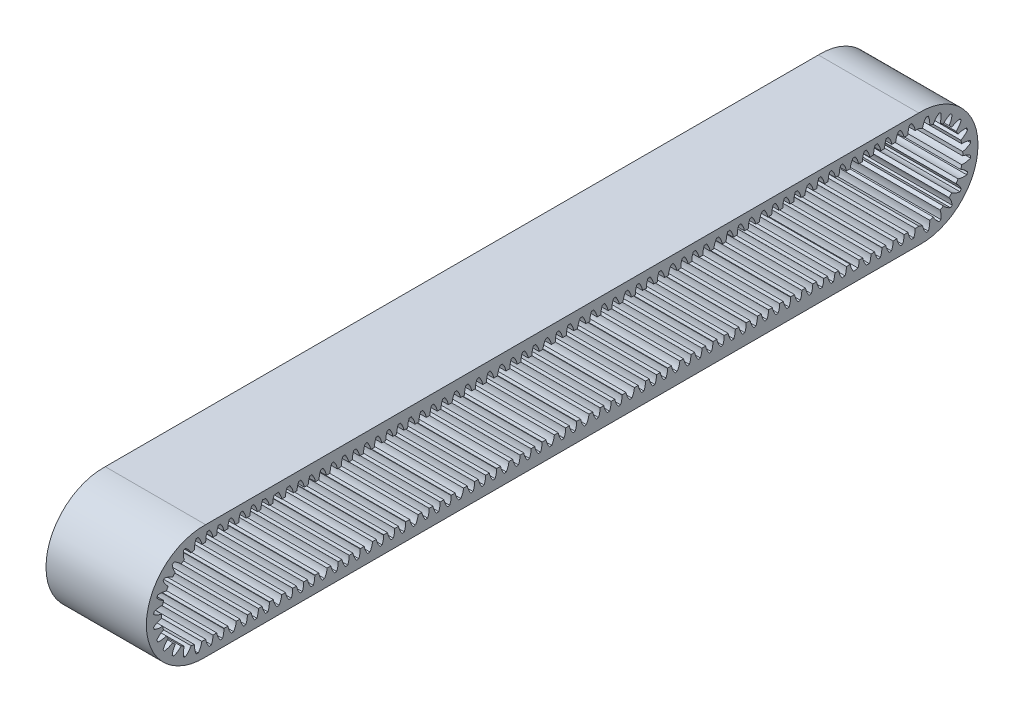
SolidWorks part; units mm, degrees
material "Rubber"
ref_plane "Front Plane" through (0, 0, 0) normal (0, 0, 1) x (1, 0, 0)
ref_plane "Top Plane" through (0, 0, 0) normal (0, 1, 0) x (1, 0, 0)
ref_plane "Right Plane" through (0, 0, 0) normal (1, 0, 0) x (0, 0, -1)
ref_plane "Plane1" through (-24.0362, 0, 0) normal (1, 0, 0) x (0, 0, -1)
sketch "Sketch1" plane through (-24.0362, 0, 0) normal (1, 0, 0) x (0, 0, -1)
  line L0 (112.0321, 33.7741) -> (-86.9109, 33.7741)
  line L5 (-86.9109, 1.7916) -> (112.0321, 1.7916)
  line L7 (-87.9491, 6.0912) -> (-87.9679, 6.0447)
  line L10 (-81.7512, 6.1541) -> (-81.8028, 6.0893)
  line L11 (-86.9109, 29.521) -> (-86.8764, 29.6927)
  line L15 (-72.2002, 6.1642) -> (-72.2019, 6.1661)
  line L16 (-69.0763, 6.229) -> (-69.1279, 6.1642)
  line L18 (-65.6746, 6.229) -> (-65.6799, 6.2313)
  line L20 (-75.2742, 6.1661) -> (-75.2826, 6.1564)
  line L22 (-59.5315, 6.2693) -> (-59.5332, 6.2712)
  line L23 (-56.4075, 6.3341) -> (-56.4592, 6.2693)
  line L25 (-53.0059, 6.3341) -> (-53.0112, 6.3364)
  line L27 (-46.8565, 6.3442) -> (-46.8582, 6.3461)
  line L28 (-43.7326, 6.409) -> (-43.7842, 6.3442)
  line L30 (-40.3309, 6.409) -> (-40.3363, 6.4113)
  line L32 (-49.9305, 6.3461) -> (-49.9389, 6.3364)
  line L33 (-62.6055, 6.2712) -> (-62.6077, 6.2313)
  line L35 (-34.1561, 6.4872) -> (-34.1579, 6.4891)
  line L36 (-31.0322, 6.5521) -> (-31.0839, 6.4872)
  line L38 (-27.6306, 6.5521) -> (-27.6359, 6.5543)
  line L40 (-21.4812, 6.5622) -> (-21.4829, 6.5641)
  line L41 (-18.3573, 6.627) -> (-18.4089, 6.5622)
  line L43 (-14.9556, 6.627) -> (-14.961, 6.6293)
  line L45 (-24.5552, 6.5641) -> (-24.5636, 6.5543)
  line L47 (-8.8125, 6.6673) -> (-8.8142, 6.6692)
  line L48 (-5.6886, 6.7321) -> (-5.7402, 6.6673)
  line L50 (-2.2869, 6.7321) -> (-2.2923, 6.7344)
  line L52 (3.8625, 6.7422) -> (3.8607, 6.7441)
  line L53 (6.9864, 6.807) -> (6.9347, 6.7422)
  line L55 (10.388, 6.807) -> (10.3827, 6.8093)
  line L57 (0.7885, 6.7441) -> (0.78, 6.7344)
  line L58 (-11.8865, 6.6692) -> (-11.8887, 6.6293)
  line L59 (-37.2301, 6.4891) -> (-37.264, 6.4113)
  line L61 (13.5155, 6.9308) -> (13.5138, 6.9327)
  line L62 (16.6394, 6.9956) -> (16.5878, 6.9308)
  line L64 (20.0411, 6.9956) -> (20.0357, 6.9979)
  line L66 (26.1905, 7.0057) -> (26.1887, 7.0076)
  line L67 (29.3144, 7.0705) -> (29.2627, 7.0057)
  line L69 (32.716, 7.0705) -> (32.7107, 7.0728)
  line L71 (23.1165, 7.0076) -> (23.108, 6.9979)
  line L73 (38.8592, 7.1108) -> (38.8575, 7.1127)
  line L74 (41.9831, 7.1756) -> (41.9315, 7.1108)
  line L76 (45.3847, 7.1756) -> (45.3794, 7.1779)
  line L78 (51.5341, 7.1857) -> (51.5324, 7.1876)
  line L79 (54.658, 7.2505) -> (54.6064, 7.1857)
  line L80 (13.0997, 4.781) -> (13.0408, 4.6577)
  line L81 (56.7243, 5.021) -> (56.7591, 4.9037)
  line L83 (48.4601, 7.1876) -> (48.4517, 7.1779)
  line L84 (35.7852, 7.1127) -> (35.783, 7.0728)
  line L85 (85.5453, 7.0189) -> (85.5297, 7.0033)
  line L86 (91.8615, 6.7472) -> (91.8607, 6.7465)
  line L87 (113.0891, 6.0447) -> (112.0981, 6.3763)
  line L88 (97.4226, 4.3147) -> (98.2668, 4.2409)
  line L91 (108.9883, 29.915) -> (109.0399, 29.9798)
  line L93 (105.5866, 29.915) -> (105.592, 29.9127)
  line L95 (99.4373, 29.9049) -> (99.439, 29.903)
  line L96 (96.3133, 29.8401) -> (96.365, 29.9049)
  line L98 (92.9117, 29.8401) -> (92.917, 29.8378)
  line L100 (102.5113, 29.903) -> (102.5197, 29.9127)
  line L102 (86.7685, 29.7998) -> (86.7703, 29.7979)
  line L103 (83.6446, 29.735) -> (83.6963, 29.7998)
  line L105 (80.243, 29.735) -> (80.2483, 29.7327)
  line L107 (74.0936, 29.7248) -> (74.0953, 29.7229)
  line L108 (70.9697, 29.66) -> (71.0213, 29.7248)
  line L110 (67.568, 29.66) -> (67.5734, 29.6577)
  line L112 (77.1676, 29.7229) -> (77.176, 29.7327)
  line L113 (89.8425, 29.7979) -> (89.8447, 29.8378)
  line L115 (61.3932, 29.5818) -> (61.3949, 29.5799)
  line L116 (58.2693, 29.517) -> (58.3209, 29.5818)
  line L118 (54.8677, 29.517) -> (54.873, 29.5147)
  line L120 (48.7183, 29.5069) -> (48.72, 29.505)
  line L121 (45.5944, 29.4421) -> (45.646, 29.5069)
  line L123 (42.1927, 29.4421) -> (42.1981, 29.4398)
  line L125 (51.7923, 29.505) -> (51.8007, 29.5147)
  line L127 (36.0496, 29.4018) -> (36.0513, 29.3999)
  line L128 (32.9257, 29.337) -> (32.9773, 29.4018)
  line L130 (29.524, 29.337) -> (29.5294, 29.3347)
  line L132 (23.3746, 29.3269) -> (23.3763, 29.3249)
  line L133 (20.2507, 29.262) -> (20.3023, 29.3269)
  line L135 (16.8491, 29.262) -> (16.8544, 29.2597)
  line L137 (26.4486, 29.3249) -> (26.4571, 29.3347)
  line L138 (39.1236, 29.3999) -> (39.1258, 29.4398)
  line L139 (64.4672, 29.5799) -> (64.5011, 29.6577)
  line L141 (13.7216, 29.1383) -> (13.7233, 29.1364)
  line L142 (10.5977, 29.0735) -> (10.6493, 29.1383)
  line L144 (7.196, 29.0735) -> (7.2014, 29.0712)
  line L146 (1.0466, 29.0634) -> (1.0483, 29.0615)
  line L147 (-2.0773, 28.9986) -> (-2.0257, 29.0634)
  line L149 (-5.4789, 28.9986) -> (-5.4736, 28.9963)
  line L151 (4.1206, 29.0615) -> (4.1291, 29.0712)
  line L153 (-11.6221, 28.9583) -> (-11.6204, 28.9564)
  line L154 (-14.746, 28.8935) -> (-14.6944, 28.9583)
  line L156 (-18.1476, 28.8935) -> (-18.1423, 28.8912)
  line L158 (-24.297, 28.8833) -> (-24.2953, 28.8814)
  line L159 (-27.4209, 28.8185) -> (-27.3693, 28.8833)
  line L160 (14.1374, 31.288) -> (14.1963, 31.4114)
  line L161 (-29.4872, 31.0481) -> (-29.522, 31.1653)
  line L163 (-21.223, 28.8814) -> (-21.2146, 28.8912)
  line L164 (-8.5481, 28.9564) -> (-8.5459, 28.9963)
  line L165 (-58.3082, 29.0501) -> (-58.2926, 29.0658)
  line L166 (-64.6244, 29.3219) -> (-64.6236, 29.3226)
  line L167 (-70.1855, 31.7543) -> (-71.0297, 31.8281)
  line L168 (112.1122, 29.9798) -> (113.0891, 29.521)
  line L170 (57.7751, 7.1388) -> (57.7651, 7.1333)
  line L171 (63.9422, 7.1361) -> (63.8989, 7.1096)
  line L172 (67.0233, 7.1807) -> (67.0145, 7.1361)
  line L173 (70.1389, 7.1622) -> (70.0956, 7.1807)
  line L174 (76.3286, 7.2109) -> (76.2799, 7.1225)
  line L175 (79.3925, 7.2482) -> (79.4009, 7.2109)
  line L176 (82.4648, 7.2482) -> (82.4552, 7.2604)
  line L178 (101.7757, 6.3899) -> (101.7324, 6.3634)
  line L179 (104.8569, 6.4345) -> (104.848, 6.3899)
  line L180 (107.9724, 6.416) -> (107.9292, 6.4345)
  line L181 (-30.5281, 28.9358) -> (-30.538, 28.9303)
  line L182 (-36.6618, 28.9594) -> (-36.7051, 28.9329)
  line L183 (-39.7774, 28.9329) -> (-39.7862, 28.8884)
  line L184 (-42.8585, 28.8884) -> (-42.9018, 28.9069)
  line L185 (-49.0429, 28.9466) -> (-49.0915, 28.8581)
  line L186 (-52.1638, 28.8581) -> (-52.1555, 28.8209)
  line L187 (-55.2181, 28.8087) -> (-55.2277, 28.8209)
  line L188 (-74.4953, 29.7056) -> (-74.5386, 29.6791)
  line L189 (-77.6109, 29.6791) -> (-77.6198, 29.6346)
  line L191 (-80.6921, 29.6346) -> (-80.7353, 29.6531)
  line L193 (-84.8768, 6.0893) -> (-84.8751, 6.0893)
  line L194 (-78.3438, 6.1559) -> (-78.3495, 6.1541)
  arc A0 (-101.4071, 19.3207) -> (-99.1775, 18.3113) centre (-98.3303, 23.1498) ccw
  arc A2 (-84.8751, 6.0893) -> (-83.8182, 6.0893) centre (-84.3466, 17.8274) ccw
  arc A6 (-87.9491, 6.0912) -> (-86.8922, 6.0912) centre (-87.4206, 17.8293) ccw
  arc A7 (-86.8922, 6.0912) -> (-85.8828, 3.8616) centre (-82.0537, 6.9383) ccw
  arc A8 (-85.8828, 3.8616) -> (-85.2909, 3.9395) centre (-87.4206, 17.8293) ccw
  arc A9 (-85.2909, 3.9395) -> (-84.8768, 6.0893) centre (-89.7859, 5.9204) ccw
  arc A10 (-83.8182, 6.0893) -> (-82.8088, 3.8597) centre (-78.9797, 6.9364) ccw
  arc A11 (-82.8088, 3.8597) -> (-82.217, 3.9376) centre (-84.3466, 17.8274) ccw
  arc A12 (-82.217, 3.9376) -> (-81.8028, 6.0893) centre (-86.7119, 5.9184) ccw
  arc A13 (-81.7512, 6.1541) -> (-80.6943, 6.1541) centre (-81.2227, 17.8922) ccw
  arc A14 (-80.6943, 6.1541) -> (-79.6849, 3.9245) centre (-75.8558, 7.0012) ccw
  arc A15 (-79.6849, 3.9245) -> (-79.093, 4.0024) centre (-81.2227, 17.8922) ccw
  arc A16 (-79.093, 4.0024) -> (-78.3495, 6.1541) centre (-83.2376, 6.6389) ccw
  arc A17 (-78.3438, 6.1559) -> (-77.298, 6.1564) centre (-77.8264, 17.8945) ccw
  arc A18 (-77.298, 6.1564) -> (-76.2886, 3.9268) centre (-72.4595, 7.0035) ccw
  arc A19 (-76.2886, 3.9268) -> (-75.6967, 4.0047) centre (-77.8264, 17.8945) ccw
  arc A20 (-75.6967, 4.0047) -> (-75.2826, 6.1564) centre (-80.1917, 5.9856) ccw
  arc A21 (-72.2002, 6.1642) -> (-71.1432, 6.1642) centre (-71.6717, 17.9023) ccw
  arc A22 (-75.2742, 6.1661) -> (-74.2172, 6.1661) centre (-74.7457, 17.9042) ccw
  arc A23 (-74.2172, 6.1661) -> (-73.2079, 3.9365) centre (-69.3787, 7.0133) ccw
  arc A24 (-73.2079, 3.9365) -> (-72.616, 4.0145) centre (-74.7457, 17.9042) ccw
  arc A25 (-72.616, 4.0145) -> (-72.2019, 6.1661) centre (-77.111, 5.9953) ccw
  arc A27 (113.0891, 6.0447) -> (114.0984, 3.8152) centre (117.9276, 6.8919) ccw
  arc A28 (114.0984, 3.8152) -> (114.6903, 3.8931) centre (112.5606, 17.7829) ccw
  arc A29 (114.6903, 3.8931) -> (115.0882, 6.3079) centre (110.1953, 5.8739) ccw
  arc A30 (115.0882, 6.3079) -> (116.1091, 6.5815) centre (112.5606, 17.7829) ccw
  arc A31 (116.1091, 6.5815) -> (117.6611, 4.6891) centre (120.5635, 8.6521) ccw
  arc A32 (117.6611, 4.6891) -> (118.2127, 4.9176) centre (112.5606, 17.7829) ccw
  arc A33 (118.2127, 4.9176) -> (117.972, 7.3531) centre (113.3582, 5.6675) ccw
  arc A34 (117.972, 7.3531) -> (118.8873, 7.8816) centre (112.5606, 17.7829) ccw
  arc A35 (118.8873, 7.8816) -> (120.8762, 6.4554) centre (122.654, 11.0345) ccw
  arc A36 (120.8762, 6.4554) -> (121.3499, 6.8188) centre (112.5606, 17.7829) ccw
  arc A37 (121.3499, 6.8188) -> (120.487, 9.1091) centre (116.4667, 6.2868) ccw
  arc A38 (120.487, 9.1091) -> (121.2344, 9.8564) centre (112.5606, 17.7829) ccw
  arc A39 (121.2344, 9.8564) -> (123.5246, 8.9936) centre (124.0567, 13.8768) ccw
  arc A40 (123.5246, 8.9936) -> (123.8881, 9.4672) centre (112.5606, 17.7829) ccw
  arc A41 (123.8881, 9.4672) -> (122.4619, 11.4561) centre (119.309, 7.6895) ccw
  arc A42 (122.4619, 11.4561) -> (122.9903, 12.3715) centre (112.5606, 17.7829) ccw
  arc A43 (122.9903, 12.3715) -> (125.4259, 12.1308) centre (124.6759, 16.9853) ccw
  arc A44 (125.4259, 12.1308) -> (125.6543, 12.6823) centre (112.5606, 17.7829) ccw
  arc A45 (125.6543, 12.6823) -> (123.762, 14.2343) centre (121.6914, 9.78) ccw
  arc A46 (123.762, 14.2343) -> (124.0355, 15.2553) centre (112.5606, 17.7829) ccw
  arc A47 (124.0355, 15.2553) -> (126.4504, 15.6532) centre (124.4695, 20.1481) ccw
  arc A48 (126.4504, 15.6532) -> (126.5283, 16.245) centre (112.5606, 17.7829) ccw
  arc A49 (126.5283, 16.245) -> (124.2987, 17.2544) centre (123.4516, 12.4159) ccw
  arc A50 (124.2987, 17.2544) -> (124.2987, 18.3113) centre (112.5606, 17.7829) ccw
  arc A51 (124.2987, 18.3113) -> (126.5283, 19.3207) centre (123.4516, 23.1498) ccw
  arc A52 (126.5283, 19.3207) -> (126.4504, 19.9125) centre (112.5606, 17.7829) ccw
  arc A53 (126.4504, 19.9125) -> (124.0355, 20.3104) centre (124.4695, 15.4176) ccw
  arc A54 (124.0355, 20.3104) -> (123.762, 21.3314) centre (112.5606, 17.7829) ccw
  arc A55 (123.762, 21.3314) -> (125.6543, 22.8834) centre (121.6914, 25.7857) ccw
  arc A56 (125.6543, 22.8834) -> (125.4259, 23.4349) centre (112.5606, 17.7829) ccw
  arc A57 (125.4259, 23.4349) -> (122.9903, 23.1942) centre (124.6759, 18.5804) ccw
  arc A58 (122.9903, 23.1942) -> (122.4619, 24.1096) centre (112.5606, 17.7829) ccw
  arc A59 (122.4619, 24.1096) -> (123.8881, 26.0985) centre (119.309, 27.8762) ccw
  arc A60 (123.8881, 26.0985) -> (123.5246, 26.5721) centre (112.5606, 17.7829) ccw
  arc A61 (123.5246, 26.5721) -> (121.2344, 25.7093) centre (124.0567, 21.6889) ccw
  arc A62 (121.2344, 25.7093) -> (120.487, 26.4566) centre (112.5606, 17.7829) ccw
  arc A63 (120.487, 26.4566) -> (121.3499, 28.7469) centre (116.4667, 29.2789) ccw
  arc A64 (121.3499, 28.7469) -> (120.8762, 29.1103) centre (112.5606, 17.7829) ccw
  arc A65 (120.8762, 29.1103) -> (118.8873, 27.6841) centre (122.654, 24.5312) ccw
  arc A66 (118.8873, 27.6841) -> (117.972, 28.2126) centre (112.5606, 17.7829) ccw
  arc A67 (117.972, 28.2126) -> (118.2127, 30.6481) centre (113.3582, 29.8982) ccw
  arc A68 (118.2127, 30.6481) -> (117.6611, 30.8766) centre (112.5606, 17.7829) ccw
  arc A69 (117.6611, 30.8766) -> (116.1091, 28.9842) centre (120.5635, 26.9136) ccw
  arc A70 (116.1091, 28.9842) -> (115.0882, 29.2578) centre (112.5606, 17.7829) ccw
  arc A71 (115.0882, 29.2578) -> (114.6903, 31.6726) centre (110.1953, 29.6918) ccw
  arc A72 (114.6903, 31.6726) -> (114.0984, 31.7505) centre (112.5606, 17.7829) ccw
  arc A73 (114.0984, 31.7505) -> (113.0891, 29.521) centre (117.9276, 28.6738) ccw
  arc A75 (-71.1432, 6.1642) -> (-70.1339, 3.9346) centre (-66.3047, 7.0114) ccw
  arc A76 (-70.1339, 3.9346) -> (-69.542, 4.0125) centre (-71.6717, 17.9023) ccw
  arc A77 (-69.542, 4.0125) -> (-69.1279, 6.1642) centre (-74.037, 5.9934) ccw
  arc A78 (-69.0763, 6.229) -> (-68.0193, 6.229) centre (-68.5478, 17.9671) ccw
  arc A79 (-68.0193, 6.229) -> (-67.01, 3.9994) centre (-63.1808, 7.0762) ccw
  arc A80 (-67.01, 3.9994) -> (-66.4181, 4.0774) centre (-68.5478, 17.9671) ccw
  arc A81 (-66.4181, 4.0774) -> (-65.6746, 6.229) centre (-70.5627, 6.7138) ccw
  arc A82 (-65.6799, 6.2313) -> (-64.623, 6.2313) centre (-65.1515, 17.9694) ccw
  arc A83 (-64.623, 6.2313) -> (-63.6137, 4.0017) centre (-59.7845, 7.0785) ccw
  arc A84 (-63.6137, 4.0017) -> (-63.0218, 4.0797) centre (-65.1515, 17.9694) ccw
  arc A85 (-63.0218, 4.0797) -> (-62.6077, 6.2313) centre (-67.5168, 6.0605) ccw
  arc A86 (-59.5315, 6.2693) -> (-58.4745, 6.2693) centre (-59.003, 18.0074) ccw
  arc A87 (-62.6055, 6.2712) -> (-61.5485, 6.2712) centre (-62.077, 18.0093) ccw
  arc A88 (-61.5485, 6.2712) -> (-60.5392, 4.0416) centre (-56.71, 7.1184) ccw
  arc A89 (-60.5392, 4.0416) -> (-59.9473, 4.1196) centre (-62.077, 18.0093) ccw
  arc A90 (-59.9473, 4.1196) -> (-59.5332, 6.2712) centre (-64.4423, 6.1004) ccw
  arc A91 (-58.4745, 6.2693) -> (-57.4652, 4.0397) centre (-53.636, 7.1165) ccw
  arc A92 (-57.4652, 4.0397) -> (-56.8733, 4.1176) centre (-59.003, 18.0074) ccw
  arc A93 (-56.8733, 4.1176) -> (-56.4592, 6.2693) centre (-61.3683, 6.0985) ccw
  arc A94 (-56.4075, 6.3341) -> (-55.3506, 6.3341) centre (-55.8791, 18.0722) ccw
  arc A95 (-55.3506, 6.3341) -> (-54.3413, 4.1045) centre (-50.5121, 7.1813) ccw
  arc A96 (-54.3413, 4.1045) -> (-53.7494, 4.1825) centre (-55.8791, 18.0722) ccw
  arc A97 (112.0321, 1.7916) -> (112.0321, 33.7741) centre (112.5606, 17.7829) ccw
  arc A98 (-99.1775, 18.3113) -> (-99.1775, 17.2544) centre (-87.4394, 17.7829) ccw
  arc A99 (-99.1775, 17.2544) -> (-101.4071, 16.245) centre (-98.3303, 12.4159) ccw
  arc A100 (-101.4071, 16.245) -> (-101.3291, 15.6532) centre (-87.4394, 17.7829) ccw
  arc A101 (-101.3291, 15.6532) -> (-98.9143, 15.2553) centre (-99.3483, 20.1481) ccw
  arc A102 (-98.9143, 15.2553) -> (-98.6408, 14.2343) centre (-87.4394, 17.7829) ccw
  arc A103 (-98.6408, 14.2343) -> (-100.5331, 12.6823) centre (-96.5702, 9.78) ccw
  arc A104 (-100.5331, 12.6823) -> (-100.2851, 12.0865) centre (-87.4394, 17.7829) ccw
  arc A105 (-100.2851, 12.0865) -> (-97.8691, 12.3715) centre (-99.6347, 16.9553) ccw
  arc A106 (-97.8691, 12.3715) -> (-97.3407, 11.4561) centre (-87.4394, 17.7829) ccw
  arc A107 (-97.3407, 11.4561) -> (-98.7668, 9.4672) centre (-94.1878, 7.6895) ccw
  arc A108 (-98.7668, 9.4672) -> (-98.4034, 8.9936) centre (-87.4394, 17.7829) ccw
  arc A109 (-98.4034, 8.9936) -> (-96.1132, 9.8564) centre (-98.9355, 13.8768) ccw
  arc A110 (-96.1132, 9.8564) -> (-95.3658, 9.1091) centre (-87.4394, 17.7829) ccw
  arc A111 (-95.3658, 9.1091) -> (-96.2286, 6.8188) centre (-91.3454, 6.2868) ccw
  arc A112 (-96.2286, 6.8188) -> (-95.755, 6.4554) centre (-87.4394, 17.7829) ccw
  arc A113 (-95.755, 6.4554) -> (-93.7661, 7.8816) centre (-97.5328, 11.0345) ccw
  arc A114 (-93.7661, 7.8816) -> (-92.8508, 7.3531) centre (-87.4394, 17.7829) ccw
  arc A115 (-92.8508, 7.3531) -> (-93.0914, 4.9176) centre (-88.2369, 5.6675) ccw
  arc A116 (-93.0914, 4.9176) -> (-92.5399, 4.6891) centre (-87.4394, 17.7829) ccw
  arc A117 (-92.5399, 4.6891) -> (-90.9879, 6.5815) centre (-95.4422, 8.6521) ccw
  arc A118 (-90.9879, 6.5815) -> (-89.967, 6.3079) centre (-87.4394, 17.7829) ccw
  arc A119 (-89.967, 6.3079) -> (-89.5691, 3.8931) centre (-85.0741, 5.8739) ccw
  arc A120 (-89.5691, 3.8931) -> (-88.9772, 3.8152) centre (-87.4394, 17.7829) ccw
  arc A121 (-88.9772, 3.8152) -> (-87.9679, 6.0447) centre (-92.8063, 6.8919) ccw
  arc A170 (-86.9109, 29.521) -> (-87.9679, 29.521) centre (-87.4394, 17.7829) ccw
  arc A171 (-87.9679, 29.521) -> (-88.9772, 31.7505) centre (-92.8063, 28.6738) ccw
  arc A172 (-88.9772, 31.7505) -> (-89.5691, 31.6726) centre (-87.4394, 17.7829) ccw
  arc A173 (-89.5691, 31.6726) -> (-89.967, 29.2578) centre (-85.0741, 29.6918) ccw
  arc A174 (-89.967, 29.2578) -> (-90.9879, 28.9842) centre (-87.4394, 17.7829) ccw
  arc A175 (-90.9879, 28.9842) -> (-92.5399, 30.8766) centre (-95.4422, 26.9136) ccw
  arc A176 (-92.5399, 30.8766) -> (-93.0914, 30.6481) centre (-87.4394, 17.7829) ccw
  arc A177 (-93.0914, 30.6481) -> (-92.8508, 28.2126) centre (-88.2369, 29.8982) ccw
  arc A178 (-92.8508, 28.2126) -> (-93.7661, 27.6841) centre (-87.4394, 17.7829) ccw
  arc A179 (-93.7661, 27.6841) -> (-95.755, 29.1103) centre (-97.5328, 24.5312) ccw
  arc A180 (-95.755, 29.1103) -> (-96.2286, 28.7469) centre (-87.4394, 17.7829) ccw
  arc A181 (-96.2286, 28.7469) -> (-95.3658, 26.4566) centre (-91.3454, 29.2789) ccw
  arc A182 (-95.3658, 26.4566) -> (-96.1132, 25.7093) centre (-87.4394, 17.7829) ccw
  arc A183 (-96.1132, 25.7093) -> (-98.4034, 26.5721) centre (-98.9355, 21.6889) ccw
  arc A184 (-98.4034, 26.5721) -> (-98.7668, 26.0985) centre (-87.4394, 17.7829) ccw
  arc A185 (-98.7668, 26.0985) -> (-97.3407, 24.1096) centre (-94.1878, 27.8762) ccw
  arc A186 (-97.3407, 24.1096) -> (-97.8691, 23.1942) centre (-87.4394, 17.7829) ccw
  arc A187 (-97.8691, 23.1942) -> (-100.3047, 23.4349) centre (-99.5547, 18.5804) ccw
  arc A188 (-100.3047, 23.4349) -> (-100.5331, 22.8834) centre (-87.4394, 17.7829) ccw
  arc A189 (-100.5331, 22.8834) -> (-98.6408, 21.3314) centre (-96.5702, 25.7857) ccw
  arc A190 (-98.6408, 21.3314) -> (-98.9143, 20.3104) centre (-87.4394, 17.7829) ccw
  arc A191 (-98.9143, 20.3104) -> (-101.3291, 19.9125) centre (-99.3483, 15.4176) ccw
  arc A192 (-101.3291, 19.9125) -> (-101.4071, 19.3207) centre (-87.4394, 17.7829) ccw
  arc A193 (-86.9109, 33.7741) -> (-86.9109, 1.7916) centre (-87.4394, 17.7829) ccw
  arc A388 (-53.7494, 4.1825) -> (-53.0059, 6.3341) centre (-57.894, 6.8189) ccw
  arc A389 (-53.0112, 6.3364) -> (-51.9543, 6.3364) centre (-52.4828, 18.0745) ccw
  arc A390 (-51.9543, 6.3364) -> (-50.945, 4.1068) centre (-47.1158, 7.1836) ccw
  arc A391 (-50.945, 4.1068) -> (-50.3531, 4.1848) centre (-52.4828, 18.0745) ccw
  arc A392 (-50.3531, 4.1848) -> (-49.9389, 6.3364) centre (-54.8481, 6.1656) ccw
  arc A393 (-46.8565, 6.3442) -> (-45.7996, 6.3442) centre (-46.328, 18.0823) ccw
  arc A394 (-49.9305, 6.3461) -> (-48.8736, 6.3461) centre (-49.402, 18.0842) ccw
  arc A395 (-48.8736, 6.3461) -> (-47.8642, 4.1166) centre (-44.0351, 7.1933) ccw
  arc A396 (-47.8642, 4.1166) -> (-47.2723, 4.1945) centre (-49.402, 18.0842) ccw
  arc A397 (-47.2723, 4.1945) -> (-46.8582, 6.3461) centre (-51.7673, 6.1753) ccw
  arc A398 (-45.7996, 6.3442) -> (-44.7902, 4.1147) centre (-40.9611, 7.1914) ccw
  arc A399 (-44.7902, 4.1147) -> (-44.1983, 4.1926) centre (-46.328, 18.0823) ccw
  arc A400 (-44.1983, 4.1926) -> (-43.7842, 6.3442) centre (-48.6933, 6.1734) ccw
  arc A401 (-43.7326, 6.409) -> (-42.6757, 6.409) centre (-43.2041, 18.1472) ccw
  arc A402 (-42.6757, 6.409) -> (-41.6663, 4.1795) centre (-37.8372, 7.2562) ccw
  arc A403 (-41.6663, 4.1795) -> (-41.0744, 4.2574) centre (-43.2041, 18.1472) ccw
  arc A404 (-41.0744, 4.2574) -> (-40.3309, 6.409) centre (-45.219, 6.8938) ccw
  arc A405 (-40.3363, 6.4113) -> (-39.2793, 6.4113) centre (-39.8078, 18.1494) ccw
  arc A406 (-39.2793, 6.4113) -> (-38.27, 4.1818) centre (-34.4409, 7.2585) ccw
  arc A407 (-38.27, 4.1818) -> (-37.6781, 4.2597) centre (-39.8078, 18.1494) ccw
  arc A408 (-37.6781, 4.2597) -> (-37.264, 6.4113) centre (-42.1731, 6.2405) ccw
  arc A409 (-34.1561, 6.4872) -> (-33.0992, 6.4872) centre (-33.6277, 18.2253) ccw
  arc A410 (-37.2301, 6.4891) -> (-36.1732, 6.4891) centre (-36.7017, 18.2273) ccw
  arc A411 (-36.1732, 6.4891) -> (-35.1639, 4.2596) centre (-31.3347, 7.3363) ccw
  arc A412 (-35.1639, 4.2596) -> (-34.572, 4.3375) centre (-36.7017, 18.2273) ccw
  arc A413 (-34.572, 4.3375) -> (-34.1579, 6.4891) centre (-39.067, 6.3183) ccw
  arc A414 (-33.0992, 6.4872) -> (-32.0899, 4.2577) centre (-28.2607, 7.3344) ccw
  arc A415 (-32.0899, 4.2577) -> (-31.498, 4.3356) centre (-33.6277, 18.2253) ccw
  arc A416 (-31.498, 4.3356) -> (-31.0839, 6.4872) centre (-35.993, 6.3164) ccw
  arc A417 (-31.0322, 6.5521) -> (-29.9753, 6.5521) centre (-30.5038, 18.2902) ccw
  arc A418 (-29.9753, 6.5521) -> (-28.966, 4.3225) centre (-25.1368, 7.3992) ccw
  arc A419 (-28.966, 4.3225) -> (-28.3741, 4.4004) centre (-30.5038, 18.2902) ccw
  arc A420 (-28.3741, 4.4004) -> (-27.6306, 6.5521) centre (-32.5187, 7.0368) ccw
  arc A421 (-27.6359, 6.5543) -> (-26.579, 6.5543) centre (-27.1075, 18.2924) ccw
  arc A422 (-26.579, 6.5543) -> (-25.5696, 4.3248) centre (-21.7405, 7.4015) ccw
  arc A423 (-25.5696, 4.3248) -> (-24.9778, 4.4027) centre (-27.1075, 18.2924) ccw
  arc A424 (-24.9778, 4.4027) -> (-24.5636, 6.5543) centre (-29.4728, 6.3835) ccw
  arc A425 (-21.4812, 6.5622) -> (-20.4243, 6.5622) centre (-20.9527, 18.3003) ccw
  arc A426 (-24.5552, 6.5641) -> (-23.4983, 6.5641) centre (-24.0267, 18.3022) ccw
  arc A427 (-23.4983, 6.5641) -> (-22.4889, 4.3345) centre (-18.6598, 7.4112) ccw
  arc A428 (-22.4889, 4.3345) -> (-21.897, 4.4124) centre (-24.0267, 18.3022) ccw
  arc A429 (-21.897, 4.4124) -> (-21.4829, 6.5641) centre (-26.392, 6.3933) ccw
  arc A430 (-20.4243, 6.5622) -> (-19.4149, 4.3326) centre (-15.5858, 7.4093) ccw
  arc A431 (-19.4149, 4.3326) -> (-18.823, 4.4105) centre (-20.9527, 18.3003) ccw
  arc A432 (-18.823, 4.4105) -> (-18.4089, 6.5622) centre (-23.318, 6.3914) ccw
  arc A433 (-18.3573, 6.627) -> (-17.3004, 6.627) centre (-17.8288, 18.3651) ccw
  arc A434 (-17.3004, 6.627) -> (-16.291, 4.3974) centre (-12.4619, 7.4741) ccw
  arc A435 (-16.291, 4.3974) -> (-15.6991, 4.4753) centre (-17.8288, 18.3651) ccw
  arc A436 (-15.6991, 4.4753) -> (-14.9556, 6.627) centre (-19.8437, 7.1118) ccw
  arc A437 (-14.961, 6.6293) -> (-13.904, 6.6293) centre (-14.4325, 18.3674) ccw
  arc A438 (-13.904, 6.6293) -> (-12.8947, 4.3997) centre (-9.0656, 7.4764) ccw
  arc A439 (-12.8947, 4.3997) -> (-12.3028, 4.4776) centre (-14.4325, 18.3674) ccw
  arc A440 (-12.3028, 4.4776) -> (-11.8887, 6.6293) centre (-16.7978, 6.4585) ccw
  arc A441 (-8.8125, 6.6673) -> (-7.7556, 6.6673) centre (-8.284, 18.4054) ccw
  arc A442 (-11.8865, 6.6692) -> (-10.8296, 6.6692) centre (-11.358, 18.4073) ccw
  arc A443 (-10.8296, 6.6692) -> (-9.8202, 4.4396) centre (-5.9911, 7.5163) ccw
  arc A444 (-9.8202, 4.4396) -> (-9.2283, 4.5175) centre (-11.358, 18.4073) ccw
  arc A445 (-9.2283, 4.5175) -> (-8.8142, 6.6692) centre (-13.7233, 6.4984) ccw
  arc A446 (-7.7556, 6.6673) -> (-6.7462, 4.4377) centre (-2.9171, 7.5144) ccw
  arc A447 (-6.7462, 4.4377) -> (-6.1543, 4.5156) centre (-8.284, 18.4054) ccw
  arc A448 (-6.1543, 4.5156) -> (-5.7402, 6.6673) centre (-10.6493, 6.4965) ccw
  arc A449 (-5.6886, 6.7321) -> (-4.6316, 6.7321) centre (-5.1601, 18.4702) ccw
  arc A450 (-4.6316, 6.7321) -> (-3.6223, 4.5025) centre (0.2068, 7.5792) ccw
  arc A451 (-3.6223, 4.5025) -> (-3.0304, 4.5804) centre (-5.1601, 18.4702) ccw
  arc A452 (-3.0304, 4.5804) -> (-2.2869, 6.7321) centre (-7.175, 7.2169) ccw
  arc A453 (-2.2923, 6.7344) -> (-1.2353, 6.7344) centre (-1.7638, 18.4725) ccw
  arc A454 (-1.2353, 6.7344) -> (-0.226, 4.5048) centre (3.6031, 7.5815) ccw
  arc A455 (-0.226, 4.5048) -> (0.3659, 4.5827) centre (-1.7638, 18.4725) ccw
  arc A456 (0.3659, 4.5827) -> (0.78, 6.7344) centre (-4.1291, 6.5636) ccw
  arc A457 (3.8625, 6.7422) -> (4.9194, 6.7422) centre (4.3909, 18.4803) ccw
  arc A458 (0.7885, 6.7441) -> (1.8454, 6.7441) centre (1.3169, 18.4822) ccw
  arc A459 (1.8454, 6.7441) -> (2.8547, 4.5145) centre (6.6839, 7.5913) ccw
  arc A460 (2.8547, 4.5145) -> (3.4466, 4.5925) centre (1.3169, 18.4822) ccw
  arc A461 (3.4466, 4.5925) -> (3.8607, 6.7441) centre (-1.0484, 6.5733) ccw
  arc A462 (4.9194, 6.7422) -> (5.9287, 4.5126) centre (9.7579, 7.5894) ccw
  arc A463 (5.9287, 4.5126) -> (6.5206, 4.5906) centre (4.3909, 18.4803) ccw
  arc A464 (6.5206, 4.5906) -> (6.9347, 6.7422) centre (2.0256, 6.5714) ccw
  arc A465 (6.9864, 6.807) -> (8.0433, 6.807) centre (7.5148, 18.5451) ccw
  arc A466 (8.0433, 6.807) -> (9.0526, 4.5775) centre (12.8818, 7.6542) ccw
  arc A467 (9.0526, 4.5775) -> (9.6445, 4.6554) centre (7.5148, 18.5451) ccw
  arc A468 (9.6445, 4.6554) -> (10.388, 6.807) centre (5.4999, 7.2918) ccw
  arc A469 (10.3827, 6.8093) -> (11.4396, 6.8093) centre (10.9111, 18.5474) ccw
  arc A470 (11.4396, 6.8093) -> (12.449, 4.5797) centre (16.2781, 7.6565) ccw
  arc A471 (12.449, 4.5797) -> (13.0408, 4.6577) centre (10.9111, 18.5474) ccw
  arc A473 (13.5155, 6.9308) -> (14.5724, 6.9308) centre (14.044, 18.6689) ccw
  arc A474 (13.0997, 4.781) -> (13.5138, 6.9327) centre (8.6047, 6.7619) ccw
  arc A475 (14.5724, 6.9308) -> (15.5818, 4.7012) centre (19.4109, 7.7779) ccw
  arc A476 (15.5818, 4.7012) -> (16.1737, 4.7791) centre (14.044, 18.6689) ccw
  arc A477 (16.1737, 4.7791) -> (16.5878, 6.9308) centre (11.6787, 6.7599) ccw
  arc A478 (16.6394, 6.9956) -> (17.6964, 6.9956) centre (17.1679, 18.7337) ccw
  arc A479 (17.6964, 6.9956) -> (18.7057, 4.766) centre (22.5348, 7.8427) ccw
  arc A480 (18.7057, 4.766) -> (19.2976, 4.8439) centre (17.1679, 18.7337) ccw
  arc A481 (19.2976, 4.8439) -> (20.0411, 6.9956) centre (15.153, 7.4804) ccw
  arc A482 (20.0357, 6.9979) -> (21.0927, 6.9979) centre (20.5642, 18.736) ccw
  arc A483 (21.0927, 6.9979) -> (22.102, 4.7683) centre (25.9311, 7.845) ccw
  arc A484 (22.102, 4.7683) -> (22.6939, 4.8462) centre (20.5642, 18.736) ccw
  arc A485 (22.6939, 4.8462) -> (23.108, 6.9979) centre (18.1989, 6.8271) ccw
  arc A486 (26.1905, 7.0057) -> (27.2474, 7.0057) centre (26.7189, 18.7438) ccw
  arc A487 (23.1165, 7.0076) -> (24.1734, 7.0076) centre (23.6449, 18.7457) ccw
  arc A488 (24.1734, 7.0076) -> (25.1827, 4.778) centre (29.0119, 7.8548) ccw
  arc A489 (25.1827, 4.778) -> (25.7746, 4.856) centre (23.6449, 18.7457) ccw
  arc A490 (25.7746, 4.856) -> (26.1887, 7.0076) centre (21.2796, 6.8368) ccw
  arc A491 (27.2474, 7.0057) -> (28.2567, 4.7761) centre (32.0859, 7.8529) ccw
  arc A492 (28.2567, 4.7761) -> (28.8486, 4.854) centre (26.7189, 18.7438) ccw
  arc A493 (28.8486, 4.854) -> (29.2627, 7.0057) centre (24.3536, 6.8349) ccw
  arc A494 (29.3144, 7.0705) -> (30.3713, 7.0705) centre (29.8428, 18.8086) ccw
  arc A495 (30.3713, 7.0705) -> (31.3806, 4.8409) centre (35.2098, 7.9177) ccw
  arc A496 (31.3806, 4.8409) -> (31.9725, 4.9189) centre (29.8428, 18.8086) ccw
  arc A497 (31.9725, 4.9189) -> (32.716, 7.0705) centre (27.8279, 7.5553) ccw
  arc A498 (32.7107, 7.0728) -> (33.7676, 7.0728) centre (33.2391, 18.8109) ccw
  arc A499 (33.7676, 7.0728) -> (34.777, 4.8432) centre (38.6061, 7.92) ccw
  arc A500 (34.777, 4.8432) -> (35.3688, 4.9211) centre (33.2391, 18.8109) ccw
  arc A501 (35.3688, 4.9211) -> (35.783, 7.0728) centre (30.8739, 6.902) ccw
  arc A502 (38.8592, 7.1108) -> (39.9161, 7.1108) centre (39.3876, 18.8489) ccw
  arc A503 (35.7852, 7.1127) -> (36.8421, 7.1127) centre (36.3136, 18.8508) ccw
  arc A504 (36.8421, 7.1127) -> (37.8514, 4.8831) centre (41.6806, 7.9599) ccw
  arc A505 (37.8514, 4.8831) -> (38.4433, 4.9611) centre (36.3136, 18.8508) ccw
  arc A506 (38.4433, 4.9611) -> (38.8575, 7.1127) centre (33.9483, 6.9419) ccw
  arc A507 (39.9161, 7.1108) -> (40.9254, 4.8812) centre (44.7546, 7.9579) ccw
  arc A508 (40.9254, 4.8812) -> (41.5173, 4.9591) centre (39.3876, 18.8489) ccw
  arc A509 (41.5173, 4.9591) -> (41.9315, 7.1108) centre (37.0223, 6.94) ccw
  arc A510 (41.9831, 7.1756) -> (43.04, 7.1756) centre (42.5115, 18.9137) ccw
  arc A511 (43.04, 7.1756) -> (44.0494, 4.946) centre (47.8785, 8.0228) ccw
  arc A512 (44.0494, 4.946) -> (44.6412, 5.024) centre (42.5115, 18.9137) ccw
  arc A513 (44.6412, 5.024) -> (45.3847, 7.1756) centre (40.4966, 7.6604) ccw
  arc A514 (45.3794, 7.1779) -> (46.4363, 7.1779) centre (45.9079, 18.916) ccw
  arc A515 (46.4363, 7.1779) -> (47.4457, 4.9483) centre (51.2748, 8.0251) ccw
  arc A516 (47.4457, 4.9483) -> (48.0375, 5.0262) centre (45.9079, 18.916) ccw
  arc A517 (48.0375, 5.0262) -> (48.4517, 7.1779) centre (43.5426, 7.0071) ccw
  arc A518 (51.5341, 7.1857) -> (52.591, 7.1857) centre (52.0626, 18.9238) ccw
  arc A519 (48.4601, 7.1876) -> (49.517, 7.1876) centre (48.9886, 18.9257) ccw
  arc A520 (49.517, 7.1876) -> (50.5264, 4.9581) centre (54.3555, 8.0348) ccw
  arc A521 (50.5264, 4.9581) -> (51.1183, 5.036) centre (48.9886, 18.9257) ccw
  arc A522 (51.1183, 5.036) -> (51.5324, 7.1876) centre (46.6233, 7.0168) ccw
  arc A523 (52.591, 7.1857) -> (53.6004, 4.9562) centre (57.4295, 8.0329) ccw
  arc A524 (53.6004, 4.9562) -> (54.1923, 5.0341) centre (52.0626, 18.9238) ccw
  arc A525 (54.1923, 5.0341) -> (54.6064, 7.1857) centre (49.6973, 7.0149) ccw
  arc A526 (54.658, 7.2505) -> (55.715, 7.2505) centre (55.1865, 18.9887) ccw
  arc A527 (55.715, 7.2505) -> (56.7243, 5.021) centre (60.5534, 8.0977) ccw
  arc A528 (85.5453, 7.0189) -> (86.6023, 7.0189) centre (86.0738, 18.757) ccw
  arc A612 (57.7751, 7.1388) -> (58.832, 7.1388) centre (58.3036, 18.8769) ccw
  arc A613 (58.832, 7.1388) -> (59.8414, 4.9092) centre (63.6705, 7.9859) ccw
  arc A614 (59.8414, 4.9092) -> (60.4333, 4.9871) centre (58.3036, 18.8769) ccw
  arc A615 (60.4333, 4.9871) -> (60.8483, 7.1087) centre (55.9383, 6.968) ccw
  arc A616 (60.8483, 7.1087) -> (61.8835, 7.1096) centre (61.3551, 18.8477) ccw
  arc A617 (61.8835, 7.1096) -> (62.8929, 4.8801) centre (66.722, 7.9568) ccw
  arc A618 (62.8929, 4.8801) -> (63.4848, 4.958) centre (61.3551, 18.8477) ccw
  arc A619 (63.4848, 4.958) -> (63.8989, 7.1096) centre (58.9898, 6.9388) ccw
  arc A620 (63.9422, 7.1361) -> (64.9991, 7.1361) centre (64.4706, 18.8742) ccw
  arc A621 (64.9991, 7.1361) -> (66.0084, 4.9066) centre (69.8376, 7.9833) ccw
  arc A622 (66.0084, 4.9066) -> (66.6003, 4.9845) centre (64.4706, 18.8742) ccw
  arc A623 (66.6003, 4.9845) -> (67.0145, 7.1361) centre (62.1053, 6.9653) ccw
  arc A624 (56.7591, 4.9037) -> (57.351, 4.9816) centre (55.2213, 18.8714) ccw
  arc A625 (57.351, 4.9816) -> (57.7651, 7.1333) centre (52.856, 6.9625) ccw
  arc A626 (67.0233, 7.1807) -> (68.0803, 7.1807) centre (67.5518, 18.9188) ccw
  arc A627 (68.0803, 7.1807) -> (69.0896, 4.9511) centre (72.9188, 8.0278) ccw
  arc A628 (69.0896, 4.9511) -> (69.6815, 5.029) centre (67.5518, 18.9188) ccw
  arc A629 (69.6815, 5.029) -> (70.0956, 7.1807) centre (65.1865, 7.0098) ccw
  arc A630 (70.1389, 7.1622) -> (71.1958, 7.1622) centre (70.6674, 18.9003) ccw
  arc A631 (71.1958, 7.1622) -> (72.2052, 4.9326) centre (76.0343, 8.0093) ccw
  arc A632 (72.2052, 4.9326) -> (72.7971, 5.0105) centre (70.6674, 18.9003) ccw
  arc A633 (72.7971, 5.0105) -> (73.2124, 7.1223) centre (68.3021, 6.9914) ccw
  arc A634 (73.2124, 7.1223) -> (74.2646, 7.1225) centre (73.7361, 18.8606) ccw
  arc A635 (74.2646, 7.1225) -> (75.2739, 4.8929) centre (79.1031, 7.9697) ccw
  arc A636 (75.2739, 4.8929) -> (75.8658, 4.9709) centre (73.7361, 18.8606) ccw
  arc A637 (75.8658, 4.9709) -> (76.2799, 7.1225) centre (71.3708, 6.9517) ccw
  arc A638 (76.3286, 7.2109) -> (77.3855, 7.2109) centre (76.8571, 18.9491) ccw
  arc A639 (77.3855, 7.2109) -> (78.3949, 4.9814) centre (82.224, 8.0581) ccw
  arc A640 (78.3949, 4.9814) -> (78.9867, 5.0593) centre (76.8571, 18.9491) ccw
  arc A641 (78.9867, 5.0593) -> (79.4009, 7.2109) centre (74.4918, 7.0401) ccw
  arc A642 (79.3925, 7.2482) -> (80.4495, 7.2482) centre (79.921, 18.9863) ccw
  arc A643 (80.4495, 7.2482) -> (81.4588, 5.0186) centre (85.288, 8.0953) ccw
  arc A644 (81.4588, 5.0186) -> (82.0507, 5.0965) centre (79.921, 18.9863) ccw
  arc A645 (82.0507, 5.0965) -> (82.4648, 7.2482) centre (77.5557, 7.0774) ccw
  arc A1096 (82.4552, 7.2604) -> (83.5121, 7.2604) centre (82.9836, 18.9985) ccw
  arc A1097 (83.5121, 7.2604) -> (84.5214, 5.0308) centre (88.3506, 8.1075) ccw
  arc A1098 (84.5214, 5.0308) -> (85.1133, 5.1087) centre (82.9836, 18.9985) ccw
  arc A1099 (85.1133, 5.1087) -> (85.5297, 7.0033) centre (80.6183, 7.0896) ccw
  arc A1100 (86.6023, 7.0189) -> (87.6116, 4.7893) centre (91.4407, 7.8661) ccw
  arc A1101 (87.6116, 4.7893) -> (88.2035, 4.8673) centre (86.0738, 18.757) ccw
  arc A1102 (88.2035, 4.8673) -> (88.6206, 6.8466) centre (83.7085, 6.8481) ccw
  arc A1103 (88.6206, 6.8466) -> (89.6766, 6.8467) centre (89.1481, 18.5848) ccw
  arc A1104 (89.6766, 6.8467) -> (90.6859, 4.6171) centre (94.515, 7.6938) ccw
  arc A1105 (90.6859, 4.6171) -> (91.4523, 4.7229) centre (89.1481, 18.5848) ccw
  arc A1106 (91.4523, 4.7229) -> (91.8607, 6.7465) centre (86.949, 6.6849) ccw
  arc A1107 (91.8615, 6.7472) -> (92.9184, 6.7472) centre (92.3899, 18.4853) ccw
  arc A1108 (92.9184, 6.7472) -> (93.8693, 4.5918) centre (97.7569, 7.5943) ccw
  arc A1109 (93.8693, 4.5918) -> (95.0902, 4.7767) centre (92.3899, 18.4853) ccw
  arc A1110 (95.0902, 4.7767) -> (95.3926, 6.5427) centre (90.481, 6.4749) ccw
  arc A1111 (95.3926, 6.5427) -> (96.4132, 6.5443) centre (95.8848, 18.2824) ccw
  arc A1112 (96.4132, 6.5443) -> (97.4226, 4.3147) centre (101.2517, 7.3915) ccw
  arc A1113 (112.1122, 29.9798) -> (111.0553, 29.9798) centre (111.5837, 18.2417) ccw
  arc A1115 (98.2668, 4.2409) -> (98.6819, 6.3625) centre (93.7718, 6.2218) ccw
  arc A1116 (98.6819, 6.3625) -> (99.7171, 6.3634) centre (99.1886, 18.1015) ccw
  arc A1117 (99.7171, 6.3634) -> (100.7264, 4.1339) centre (104.5555, 7.2106) ccw
  arc A1118 (100.7264, 4.1339) -> (101.3183, 4.2118) centre (99.1886, 18.1015) ccw
  arc A1119 (101.3183, 4.2118) -> (101.7324, 6.3634) centre (96.8233, 6.1926) ccw
  arc A1120 (101.7757, 6.3899) -> (102.8326, 6.3899) centre (102.3042, 18.1281) ccw
  arc A1121 (102.8326, 6.3899) -> (103.842, 4.1604) centre (107.6711, 7.2371) ccw
  arc A1122 (103.842, 4.1604) -> (104.4339, 4.2383) centre (102.3042, 18.1281) ccw
  arc A1123 (104.4339, 4.2383) -> (104.848, 6.3899) centre (99.9389, 6.2191) ccw
  arc A1124 (104.8569, 6.4345) -> (105.9138, 6.4345) centre (105.3853, 18.1726) ccw
  arc A1125 (105.9138, 6.4345) -> (106.9231, 4.2049) centre (110.7523, 7.2816) ccw
  arc A1126 (106.9231, 4.2049) -> (107.515, 4.2828) centre (105.3853, 18.1726) ccw
  arc A1127 (107.515, 4.2828) -> (107.9292, 6.4345) centre (103.02, 6.2637) ccw
  arc A1128 (107.9724, 6.416) -> (109.0294, 6.416) centre (108.5009, 18.1541) ccw
  arc A1129 (109.0294, 6.416) -> (110.0387, 4.1864) centre (113.8678, 7.2631) ccw
  arc A1130 (110.0387, 4.1864) -> (110.6306, 4.2643) centre (108.5009, 18.1541) ccw
  arc A1131 (110.6306, 4.2643) -> (111.0459, 6.3761) centre (106.1356, 6.2452) ccw
  arc A1132 (111.0459, 6.3761) -> (112.0981, 6.3763) centre (111.5696, 18.1144) ccw
  arc A1133 (111.0553, 29.9798) -> (110.0459, 32.2094) centre (106.2168, 29.1326) ccw
  arc A1134 (110.0459, 32.2094) -> (109.454, 32.1315) centre (111.5837, 18.2417) ccw
  arc A1135 (109.454, 32.1315) -> (109.0399, 29.9798) centre (113.949, 30.1506) ccw
  arc A1136 (108.9883, 29.915) -> (107.9313, 29.915) centre (108.4598, 18.1769) ccw
  arc A1137 (107.9313, 29.915) -> (106.922, 32.1446) centre (103.0929, 29.0678) ccw
  arc A1138 (106.922, 32.1446) -> (106.3301, 32.0666) centre (108.4598, 18.1769) ccw
  arc A1139 (106.3301, 32.0666) -> (105.5866, 29.915) centre (110.4747, 29.4302) ccw
  arc A1140 (105.592, 29.9127) -> (104.535, 29.9127) centre (105.0635, 18.1746) ccw
  arc A1141 (104.535, 29.9127) -> (103.5257, 32.1423) centre (99.6966, 29.0655) ccw
  arc A1142 (103.5257, 32.1423) -> (102.9338, 32.0643) centre (105.0635, 18.1746) ccw
  arc A1143 (102.9338, 32.0643) -> (102.5197, 29.9127) centre (107.4288, 30.0835) ccw
  arc A1144 (99.4373, 29.9049) -> (98.3803, 29.9049) centre (98.9088, 18.1668) ccw
  arc A1145 (102.5113, 29.903) -> (101.4543, 29.903) centre (101.9828, 18.1648) ccw
  arc A1146 (101.4543, 29.903) -> (100.445, 32.1325) centre (96.6158, 29.0558) ccw
  arc A1147 (100.445, 32.1325) -> (99.8531, 32.0546) centre (101.9828, 18.1648) ccw
  arc A1148 (99.8531, 32.0546) -> (99.439, 29.903) centre (104.3481, 30.0738) ccw
  arc A1149 (98.3803, 29.9049) -> (97.371, 32.1344) centre (93.5418, 29.0577) ccw
  arc A1150 (97.371, 32.1344) -> (96.7791, 32.0565) centre (98.9088, 18.1668) ccw
  arc A1151 (96.7791, 32.0565) -> (96.365, 29.9049) centre (101.2741, 30.0757) ccw
  arc A1152 (96.3133, 29.8401) -> (95.2564, 29.8401) centre (95.7849, 18.1019) ccw
  arc A1153 (95.2564, 29.8401) -> (94.2471, 32.0696) centre (90.4179, 28.9929) ccw
  arc A1154 (94.2471, 32.0696) -> (93.6552, 31.9917) centre (95.7849, 18.1019) ccw
  arc A1155 (93.6552, 31.9917) -> (92.9117, 29.8401) centre (97.7998, 29.3553) ccw
  arc A1156 (92.917, 29.8378) -> (91.8601, 29.8378) centre (92.3886, 18.0997) ccw
  arc A1157 (91.8601, 29.8378) -> (90.8508, 32.0673) centre (87.0216, 28.9906) ccw
  arc A1158 (90.8508, 32.0673) -> (90.2589, 31.9894) centre (92.3886, 18.0997) ccw
  arc A1159 (90.2589, 31.9894) -> (89.8447, 29.8378) centre (94.7539, 30.0086) ccw
  arc A1160 (86.7685, 29.7998) -> (85.7116, 29.7998) centre (86.2401, 18.0617) ccw
  arc A1161 (89.8425, 29.7979) -> (88.7856, 29.7979) centre (89.3141, 18.0598) ccw
  arc A1162 (88.7856, 29.7979) -> (87.7763, 32.0274) centre (83.9471, 28.9507) ccw
  arc A1163 (87.7763, 32.0274) -> (87.1844, 31.9495) centre (89.3141, 18.0598) ccw
  arc A1164 (87.1844, 31.9495) -> (86.7703, 29.7979) centre (91.6794, 29.9687) ccw
  arc A1165 (85.7116, 29.7998) -> (84.7023, 32.0293) centre (80.8731, 28.9526) ccw
  arc A1166 (84.7023, 32.0293) -> (84.1104, 31.9514) centre (86.2401, 18.0617) ccw
  arc A1167 (84.1104, 31.9514) -> (83.6963, 29.7998) centre (88.6054, 29.9706) ccw
  arc A1168 (83.6446, 29.735) -> (82.5877, 29.735) centre (83.1162, 17.9968) ccw
  arc A1169 (82.5877, 29.735) -> (81.5783, 31.9645) centre (77.7492, 28.8878) ccw
  arc A1170 (81.5783, 31.9645) -> (80.9865, 31.8866) centre (83.1162, 17.9968) ccw
  arc A1171 (80.9865, 31.8866) -> (80.243, 29.735) centre (85.1311, 29.2502) ccw
  arc A1172 (80.2483, 29.7327) -> (79.1914, 29.7327) centre (79.7199, 17.9946) ccw
  arc A1173 (79.1914, 29.7327) -> (78.182, 31.9622) centre (74.3529, 28.8855) ccw
  arc A1174 (78.182, 31.9622) -> (77.5902, 31.8843) centre (79.7199, 17.9946) ccw
  arc A1175 (77.5902, 31.8843) -> (77.176, 29.7327) centre (82.0851, 29.9035) ccw
  arc A1176 (74.0936, 29.7248) -> (73.0367, 29.7248) centre (73.5651, 17.9867) ccw
  arc A1177 (77.1676, 29.7229) -> (76.1107, 29.7229) centre (76.6391, 17.9848) ccw
  arc A1178 (76.1107, 29.7229) -> (75.1013, 31.9525) centre (71.2722, 28.8758) ccw
  arc A1179 (75.1013, 31.9525) -> (74.5094, 31.8746) centre (76.6391, 17.9848) ccw
  arc A1180 (74.5094, 31.8746) -> (74.0953, 29.7229) centre (79.0044, 29.8937) ccw
  arc A1181 (73.0367, 29.7248) -> (72.0273, 31.9544) centre (68.1982, 28.8777) ccw
  arc A1182 (72.0273, 31.9544) -> (71.4354, 31.8765) centre (73.5651, 17.9867) ccw
  arc A1183 (71.4354, 31.8765) -> (71.0213, 29.7248) centre (75.9304, 29.8956) ccw
  arc A1184 (70.9697, 29.66) -> (69.9127, 29.66) centre (70.4412, 17.9219) ccw
  arc A1185 (69.9127, 29.66) -> (68.9034, 31.8896) centre (65.0743, 28.8129) ccw
  arc A1186 (68.9034, 31.8896) -> (68.3115, 31.8117) centre (70.4412, 17.9219) ccw
  arc A1187 (68.3115, 31.8117) -> (67.568, 29.66) centre (72.4561, 29.1752) ccw
  arc A1188 (67.5734, 29.6577) -> (66.5164, 29.6577) centre (67.0449, 17.9196) ccw
  arc A1189 (66.5164, 29.6577) -> (65.5071, 31.8873) centre (61.678, 28.8106) ccw
  arc A1190 (65.5071, 31.8873) -> (64.9152, 31.8094) centre (67.0449, 17.9196) ccw
  arc A1191 (64.9152, 31.8094) -> (64.5011, 29.6577) centre (69.4102, 29.8285) ccw
  arc A1192 (61.3932, 29.5818) -> (60.3363, 29.5818) centre (60.8648, 17.8437) ccw
  arc A1193 (64.4672, 29.5799) -> (63.4103, 29.5799) centre (63.9388, 17.8418) ccw
  arc A1194 (63.4103, 29.5799) -> (62.401, 31.8095) centre (58.5718, 28.7328) ccw
  arc A1195 (62.401, 31.8095) -> (61.8091, 31.7316) centre (63.9388, 17.8418) ccw
  arc A1196 (61.8091, 31.7316) -> (61.3949, 29.5799) centre (66.3041, 29.7507) ccw
  arc A1197 (60.3363, 29.5818) -> (59.327, 31.8114) centre (55.4978, 28.7347) ccw
  arc A1198 (59.327, 31.8114) -> (58.7351, 31.7335) centre (60.8648, 17.8437) ccw
  arc A1199 (58.7351, 31.7335) -> (58.3209, 29.5818) centre (63.2301, 29.7526) ccw
  arc A1200 (58.2693, 29.517) -> (57.2124, 29.517) centre (57.7409, 17.7789) ccw
  arc A1201 (57.2124, 29.517) -> (56.203, 31.7466) centre (52.3739, 28.6699) ccw
  arc A1202 (56.203, 31.7466) -> (55.6112, 31.6687) centre (57.7409, 17.7789) ccw
  arc A1203 (55.6112, 31.6687) -> (54.8677, 29.517) centre (59.7558, 29.0322) ccw
  arc A1204 (54.873, 29.5147) -> (53.8161, 29.5147) centre (54.3446, 17.7766) ccw
  arc A1205 (53.8161, 29.5147) -> (52.8067, 31.7443) centre (48.9776, 28.6676) ccw
  arc A1206 (52.8067, 31.7443) -> (52.2149, 31.6664) centre (54.3446, 17.7766) ccw
  arc A1207 (52.2149, 31.6664) -> (51.8007, 29.5147) centre (56.7098, 29.6855) ccw
  arc A1208 (48.7183, 29.5069) -> (47.6614, 29.5069) centre (48.1898, 17.7688) ccw
  arc A1209 (51.7923, 29.505) -> (50.7354, 29.505) centre (51.2638, 17.7669) ccw
  arc A1210 (50.7354, 29.505) -> (49.726, 31.7346) centre (45.8969, 28.6578) ccw
  arc A1211 (49.726, 31.7346) -> (49.1341, 31.6566) centre (51.2638, 17.7669) ccw
  arc A1212 (49.1341, 31.6566) -> (48.72, 29.505) centre (53.6291, 29.6758) ccw
  arc A1213 (47.6614, 29.5069) -> (46.652, 31.7365) centre (42.8229, 28.6597) ccw
  arc A1214 (46.652, 31.7365) -> (46.0601, 31.6585) centre (48.1898, 17.7688) ccw
  arc A1215 (46.0601, 31.6585) -> (45.646, 29.5069) centre (50.5551, 29.6777) ccw
  arc A1216 (45.5944, 29.4421) -> (44.5374, 29.4421) centre (45.0659, 17.704) ccw
  arc A1217 (44.5374, 29.4421) -> (43.5281, 31.6716) centre (39.699, 28.5949) ccw
  arc A1218 (43.5281, 31.6716) -> (42.9362, 31.5937) centre (45.0659, 17.704) ccw
  arc A1219 (42.9362, 31.5937) -> (42.1927, 29.4421) centre (47.0808, 28.9573) ccw
  arc A1220 (42.1981, 29.4398) -> (41.1411, 29.4398) centre (41.6696, 17.7017) ccw
  arc A1221 (41.1411, 29.4398) -> (40.1318, 31.6694) centre (36.3027, 28.5926) ccw
  arc A1222 (40.1318, 31.6694) -> (39.5399, 31.5914) centre (41.6696, 17.7017) ccw
  arc A1223 (39.5399, 31.5914) -> (39.1258, 29.4398) centre (44.0349, 29.6106) ccw
  arc A1224 (36.0496, 29.4018) -> (34.9926, 29.4018) centre (35.5211, 17.6637) ccw
  arc A1225 (39.1236, 29.3999) -> (38.0666, 29.3999) centre (38.5951, 17.6618) ccw
  arc A1226 (38.0666, 29.3999) -> (37.0573, 31.6295) centre (33.2282, 28.5527) ccw
  arc A1227 (37.0573, 31.6295) -> (36.4654, 31.5515) centre (38.5951, 17.6618) ccw
  arc A1228 (36.4654, 31.5515) -> (36.0513, 29.3999) centre (40.9604, 29.5707) ccw
  arc A1229 (34.9926, 29.4018) -> (33.9833, 31.6314) centre (30.1542, 28.5546) ccw
  arc A1230 (33.9833, 31.6314) -> (33.3914, 31.5534) centre (35.5211, 17.6637) ccw
  arc A1231 (33.3914, 31.5534) -> (32.9773, 29.4018) centre (37.8864, 29.5726) ccw
  arc A1232 (32.9257, 29.337) -> (31.8687, 29.337) centre (32.3972, 17.5989) ccw
  arc A1233 (31.8687, 29.337) -> (30.8594, 31.5665) centre (27.0303, 28.4898) ccw
  arc A1234 (30.8594, 31.5665) -> (30.2675, 31.4886) centre (32.3972, 17.5989) ccw
  arc A1235 (30.2675, 31.4886) -> (29.524, 29.337) centre (34.4121, 28.8522) ccw
  arc A1236 (29.5294, 29.3347) -> (28.4724, 29.3347) centre (29.0009, 17.5966) ccw
  arc A1237 (28.4724, 29.3347) -> (27.4631, 31.5643) centre (23.6339, 28.4875) ccw
  arc A1238 (27.4631, 31.5643) -> (26.8712, 31.4863) centre (29.0009, 17.5966) ccw
  arc A1239 (26.8712, 31.4863) -> (26.4571, 29.3347) centre (31.3662, 29.5055) ccw
  arc A1240 (23.3746, 29.3269) -> (22.3177, 29.3269) centre (22.8462, 17.5887) ccw
  arc A1241 (26.4486, 29.3249) -> (25.3917, 29.3249) centre (25.9202, 17.5868) ccw
  arc A1242 (25.3917, 29.3249) -> (24.3824, 31.5545) centre (20.5532, 28.4778) ccw
  arc A1243 (24.3824, 31.5545) -> (23.7905, 31.4766) centre (25.9202, 17.5868) ccw
  arc A1244 (23.7905, 31.4766) -> (23.3763, 29.3249) centre (28.2855, 29.4958) ccw
  arc A1245 (22.3177, 29.3269) -> (21.3084, 31.5564) centre (17.4792, 28.4797) ccw
  arc A1246 (21.3084, 31.5564) -> (20.7165, 31.4785) centre (22.8462, 17.5887) ccw
  arc A1247 (20.7165, 31.4785) -> (20.3023, 29.3269) centre (25.2115, 29.4977) ccw
  arc A1248 (20.2507, 29.262) -> (19.1938, 29.262) centre (19.7223, 17.5239) ccw
  arc A1249 (19.1938, 29.262) -> (18.1844, 31.4916) centre (14.3553, 28.4149) ccw
  arc A1250 (18.1844, 31.4916) -> (17.5926, 31.4137) centre (19.7223, 17.5239) ccw
  arc A1251 (17.5926, 31.4137) -> (16.8491, 29.262) centre (21.7372, 28.7772) ccw
  arc A1252 (16.8544, 29.2597) -> (15.7975, 29.2597) centre (16.326, 17.5216) ccw
  arc A1253 (15.7975, 29.2597) -> (14.7881, 31.4893) centre (10.959, 28.4126) ccw
  arc A1254 (14.7881, 31.4893) -> (14.1963, 31.4114) centre (16.326, 17.5216) ccw
  arc A1255 (13.7216, 29.1383) -> (12.6646, 29.1383) centre (13.1931, 17.4002) ccw
  arc A1256 (14.1374, 31.288) -> (13.7233, 29.1364) centre (18.6324, 29.3072) ccw
  arc A1257 (12.6646, 29.1383) -> (11.6553, 31.3679) centre (7.8262, 28.2911) ccw
  arc A1258 (11.6553, 31.3679) -> (11.0634, 31.29) centre (13.1931, 17.4002) ccw
  arc A1259 (11.0634, 31.29) -> (10.6493, 29.1383) centre (15.5584, 29.3091) ccw
  arc A1260 (10.5977, 29.0735) -> (9.5407, 29.0735) centre (10.0692, 17.3354) ccw
  arc A1261 (9.5407, 29.0735) -> (8.5314, 31.3031) centre (4.7023, 28.2263) ccw
  arc A1262 (8.5314, 31.3031) -> (7.9395, 31.2251) centre (10.0692, 17.3354) ccw
  arc A1263 (7.9395, 31.2251) -> (7.196, 29.0735) centre (12.0841, 28.5887) ccw
  arc A1264 (7.2014, 29.0712) -> (6.1444, 29.0712) centre (6.6729, 17.3331) ccw
  arc A1265 (6.1444, 29.0712) -> (5.1351, 31.3008) centre (1.3059, 28.224) ccw
  arc A1266 (5.1351, 31.3008) -> (4.5432, 31.2229) centre (6.6729, 17.3331) ccw
  arc A1267 (4.5432, 31.2229) -> (4.1291, 29.0712) centre (9.0382, 29.242) ccw
  arc A1268 (1.0466, 29.0634) -> (-0.0103, 29.0634) centre (0.5182, 17.3253) ccw
  arc A1269 (4.1206, 29.0615) -> (3.0637, 29.0615) centre (3.5922, 17.3234) ccw
  arc A1270 (3.0637, 29.0615) -> (2.0544, 31.291) centre (-1.7748, 28.2143) ccw
  arc A1271 (2.0544, 31.291) -> (1.4625, 31.2131) centre (3.5922, 17.3234) ccw
  arc A1272 (1.4625, 31.2131) -> (1.0483, 29.0615) centre (5.9575, 29.2323) ccw
  arc A1273 (-0.0103, 29.0634) -> (-1.0196, 31.2929) centre (-4.8488, 28.2162) ccw
  arc A1274 (-1.0196, 31.2929) -> (-1.6115, 31.215) centre (0.5182, 17.3253) ccw
  arc A1275 (-1.6115, 31.215) -> (-2.0257, 29.0634) centre (2.8835, 29.2342) ccw
  arc A1276 (-2.0773, 28.9986) -> (-3.1342, 28.9986) centre (-2.6057, 17.2604) ccw
  arc A1277 (-3.1342, 28.9986) -> (-4.1436, 31.2281) centre (-7.9727, 28.1514) ccw
  arc A1278 (-4.1436, 31.2281) -> (-4.7354, 31.1502) centre (-2.6057, 17.2604) ccw
  arc A1279 (-4.7354, 31.1502) -> (-5.4789, 28.9986) centre (-0.5908, 28.5138) ccw
  arc A1280 (-5.4736, 28.9963) -> (-6.5305, 28.9963) centre (-6.002, 17.2582) ccw
  arc A1281 (-6.5305, 28.9963) -> (-7.5399, 31.2258) centre (-11.369, 28.1491) ccw
  arc A1282 (-7.5399, 31.2258) -> (-8.1317, 31.1479) centre (-6.002, 17.2582) ccw
  arc A1283 (-8.1317, 31.1479) -> (-8.5459, 28.9963) centre (-3.6368, 29.1671) ccw
  arc A1284 (-11.6221, 28.9583) -> (-12.679, 28.9583) centre (-12.1505, 17.2202) ccw
  arc A1285 (-8.5481, 28.9564) -> (-9.605, 28.9564) centre (-9.0765, 17.2183) ccw
  arc A1286 (-9.605, 28.9564) -> (-10.6144, 31.1859) centre (-14.4435, 28.1092) ccw
  arc A1287 (-10.6144, 31.1859) -> (-11.2062, 31.108) centre (-9.0765, 17.2183) ccw
  arc A1288 (-11.2062, 31.108) -> (-11.6204, 28.9564) centre (-6.7113, 29.1272) ccw
  arc A1289 (-12.679, 28.9583) -> (-13.6884, 31.1878) centre (-17.5175, 28.1111) ccw
  arc A1290 (-13.6884, 31.1878) -> (-14.2802, 31.1099) centre (-12.1505, 17.2202) ccw
  arc A1291 (-14.2802, 31.1099) -> (-14.6944, 28.9583) centre (-9.7853, 29.1291) ccw
  arc A1292 (-14.746, 28.8935) -> (-15.8029, 28.8935) centre (-15.2745, 17.1553) ccw
  arc A1293 (-15.8029, 28.8935) -> (-16.8123, 31.123) centre (-20.6414, 28.0463) ccw
  arc A1294 (-16.8123, 31.123) -> (-17.4041, 31.0451) centre (-15.2745, 17.1553) ccw
  arc A1295 (-17.4041, 31.0451) -> (-18.1476, 28.8935) centre (-13.2595, 28.4087) ccw
  arc A1296 (-18.1423, 28.8912) -> (-19.1992, 28.8912) centre (-18.6708, 17.1531) ccw
  arc A1297 (-19.1992, 28.8912) -> (-20.2086, 31.1207) centre (-24.0377, 28.044) ccw
  arc A1298 (-20.2086, 31.1207) -> (-20.8005, 31.0428) centre (-18.6708, 17.1531) ccw
  arc A1299 (-20.8005, 31.0428) -> (-21.2146, 28.8912) centre (-16.3055, 29.062) ccw
  arc A1300 (-24.297, 28.8833) -> (-25.354, 28.8833) centre (-24.8255, 17.1452) ccw
  arc A1301 (-21.223, 28.8814) -> (-22.28, 28.8814) centre (-21.7515, 17.1433) ccw
  arc A1302 (-22.28, 28.8814) -> (-23.2893, 31.111) centre (-27.1184, 28.0343) ccw
  arc A1303 (-23.2893, 31.111) -> (-23.8812, 31.0331) centre (-21.7515, 17.1433) ccw
  arc A1304 (-23.8812, 31.0331) -> (-24.2953, 28.8814) centre (-19.3862, 29.0522) ccw
  arc A1305 (-25.354, 28.8833) -> (-26.3633, 31.1129) centre (-30.1924, 28.0362) ccw
  arc A1306 (-26.3633, 31.1129) -> (-26.9552, 31.035) centre (-24.8255, 17.1452) ccw
  arc A1307 (-26.9552, 31.035) -> (-27.3693, 28.8833) centre (-22.4602, 29.0541) ccw
  arc A1308 (-27.4209, 28.8185) -> (-28.4779, 28.8185) centre (-27.9494, 17.0804) ccw
  arc A1309 (-28.4779, 28.8185) -> (-29.4872, 31.0481) centre (-33.3164, 27.9714) ccw
  arc A1310 (-58.3082, 29.0501) -> (-59.3652, 29.0501) centre (-58.8367, 17.312) ccw
  arc A1311 (-84.861, 29.6927) -> (-85.8704, 31.9223) centre (-89.6995, 28.8456) ccw
  arc A1312 (-85.8704, 31.9223) -> (-86.4622, 31.8444) centre (-84.3326, 17.9546) ccw
  arc A1313 (-86.4622, 31.8444) -> (-86.8764, 29.6927) centre (-81.9673, 29.8635) ccw
  arc A1314 (-30.538, 28.9303) -> (-31.5949, 28.9303) centre (-31.0665, 17.1922) ccw
  arc A1315 (-31.5949, 28.9303) -> (-32.6043, 31.1599) centre (-36.4334, 28.0831) ccw
  arc A1316 (-32.6043, 31.1599) -> (-33.1962, 31.0819) centre (-31.0665, 17.1922) ccw
  arc A1317 (-33.1962, 31.0819) -> (-33.6113, 28.9604) centre (-28.7012, 29.1011) ccw
  arc A1318 (-33.6113, 28.9604) -> (-34.6464, 28.9594) centre (-34.118, 17.2213) ccw
  arc A1319 (-34.6464, 28.9594) -> (-35.6558, 31.189) centre (-39.4849, 28.1123) ccw
  arc A1320 (-35.6558, 31.189) -> (-36.2477, 31.1111) centre (-34.118, 17.2213) ccw
  arc A1321 (-36.2477, 31.1111) -> (-36.6618, 28.9594) centre (-31.7527, 29.1303) ccw
  arc A1322 (-36.7051, 28.9329) -> (-37.762, 28.9329) centre (-37.2335, 17.1948) ccw
  arc A1323 (-37.762, 28.9329) -> (-38.7714, 31.1625) centre (-42.6005, 28.0858) ccw
  arc A1324 (-38.7714, 31.1625) -> (-39.3632, 31.0846) centre (-37.2335, 17.1948) ccw
  arc A1325 (-39.3632, 31.0846) -> (-39.7774, 28.9329) centre (-34.8683, 29.1037) ccw
  arc A1326 (-29.522, 31.1653) -> (-30.1139, 31.0874) centre (-27.9842, 17.1977) ccw
  arc A1327 (-30.1139, 31.0874) -> (-30.5281, 28.9358) centre (-25.6189, 29.1066) ccw
  arc A1328 (-39.7862, 28.8884) -> (-40.8432, 28.8884) centre (-40.3147, 17.1503) ccw
  arc A1329 (-40.8432, 28.8884) -> (-41.8525, 31.118) centre (-45.6817, 28.0412) ccw
  arc A1330 (-41.8525, 31.118) -> (-42.4444, 31.0401) centre (-40.3147, 17.1503) ccw
  arc A1331 (-42.4444, 31.0401) -> (-42.8585, 28.8884) centre (-37.9494, 29.0592) ccw
  arc A1332 (-42.9018, 28.9069) -> (-43.9587, 28.9069) centre (-43.4303, 17.1688) ccw
  arc A1333 (-43.9587, 28.9069) -> (-44.9681, 31.1365) centre (-48.7972, 28.0597) ccw
  arc A1334 (-44.9681, 31.1365) -> (-45.56, 31.0585) centre (-43.4303, 17.1688) ccw
  arc A1335 (-45.56, 31.0585) -> (-45.9753, 28.9468) centre (-41.065, 29.0777) ccw
  arc A1336 (-45.9753, 28.9468) -> (-47.0275, 28.9466) centre (-46.499, 17.2084) ccw
  arc A1337 (-47.0275, 28.9466) -> (-48.0368, 31.1761) centre (-51.866, 28.0994) ccw
  arc A1338 (-48.0368, 31.1761) -> (-48.6287, 31.0982) centre (-46.499, 17.2084) ccw
  arc A1339 (-48.6287, 31.0982) -> (-49.0429, 28.9466) centre (-44.1337, 29.1174) ccw
  arc A1340 (-49.0915, 28.8581) -> (-50.1484, 28.8581) centre (-49.62, 17.12) ccw
  arc A1341 (-50.1484, 28.8581) -> (-51.1578, 31.0877) centre (-54.9869, 28.011) ccw
  arc A1342 (-51.1578, 31.0877) -> (-51.7496, 31.0098) centre (-49.62, 17.12) ccw
  arc A1343 (-51.7496, 31.0098) -> (-52.1638, 28.8581) centre (-47.2547, 29.0289) ccw
  arc A1344 (-52.1555, 28.8209) -> (-53.2124, 28.8209) centre (-52.6839, 17.0828) ccw
  arc A1345 (-53.2124, 28.8209) -> (-54.2217, 31.0504) centre (-58.0509, 27.9737) ccw
  arc A1346 (-54.2217, 31.0504) -> (-54.8136, 30.9725) centre (-52.6839, 17.0828) ccw
  arc A1347 (-54.8136, 30.9725) -> (-55.2277, 28.8209) centre (-50.3186, 28.9917) ccw
  arc A1348 (-55.2181, 28.8087) -> (-56.275, 28.8087) centre (-55.7465, 17.0706) ccw
  arc A1349 (-56.275, 28.8087) -> (-57.2843, 31.0383) centre (-61.1135, 27.9615) ccw
  arc A1350 (-57.2843, 31.0383) -> (-57.8762, 30.9603) centre (-55.7465, 17.0706) ccw
  arc A1351 (-57.8762, 30.9603) -> (-58.2926, 29.0658) centre (-53.3812, 28.9795) ccw
  arc A1352 (-59.3652, 29.0501) -> (-60.3745, 31.2797) centre (-64.2036, 28.203) ccw
  arc A1353 (-60.3745, 31.2797) -> (-60.9664, 31.2018) centre (-58.8367, 17.312) ccw
  arc A1354 (-60.9664, 31.2018) -> (-61.3835, 29.2224) centre (-56.4714, 29.221) ccw
  arc A1355 (-61.3835, 29.2224) -> (-62.4395, 29.2224) centre (-61.911, 17.4843) ccw
  arc A1356 (-62.4395, 29.2224) -> (-63.4488, 31.452) centre (-67.2779, 28.3752) ccw
  arc A1357 (-63.4488, 31.452) -> (-64.2152, 31.3462) centre (-61.911, 17.4843) ccw
  arc A1358 (-64.2152, 31.3462) -> (-64.6236, 29.3226) centre (-59.7119, 29.3841) ccw
  arc A1359 (-64.6244, 29.3219) -> (-65.6813, 29.3219) centre (-65.1528, 17.5838) ccw
  arc A1360 (-65.6813, 29.3219) -> (-66.6322, 31.4773) centre (-70.5198, 28.4747) ccw
  arc A1361 (-66.6322, 31.4773) -> (-67.8531, 31.2924) centre (-65.1528, 17.5838) ccw
  arc A1362 (-67.8531, 31.2924) -> (-68.1556, 29.5263) centre (-63.2439, 29.5942) ccw
  arc A1363 (-68.1556, 29.5263) -> (-69.1761, 29.5248) centre (-68.6477, 17.7867) ccw
  arc A1364 (-69.1761, 29.5248) -> (-70.1855, 31.7543) centre (-74.0146, 28.6776) ccw
  arc A1365 (-71.0297, 31.8281) -> (-71.4448, 29.7066) centre (-66.5347, 29.8473) ccw
  arc A1366 (-71.4448, 29.7066) -> (-72.48, 29.7056) centre (-71.9515, 17.9675) ccw
  arc A1367 (-72.48, 29.7056) -> (-73.4893, 31.9352) centre (-77.3185, 28.8585) ccw
  arc A1368 (-73.4893, 31.9352) -> (-74.0812, 31.8573) centre (-71.9515, 17.9675) ccw
  arc A1369 (-74.0812, 31.8573) -> (-74.4953, 29.7056) centre (-69.5862, 29.8764) ccw
  arc A1370 (-74.5386, 29.6791) -> (-75.5955, 29.6791) centre (-75.0671, 17.941) ccw
  arc A1371 (-75.5955, 29.6791) -> (-76.6049, 31.9087) centre (-80.434, 28.832) ccw
  arc A1372 (-76.6049, 31.9087) -> (-77.1968, 31.8308) centre (-75.0671, 17.941) ccw
  arc A1373 (-77.1968, 31.8308) -> (-77.6109, 29.6791) centre (-72.7018, 29.8499) ccw
  arc A1374 (-77.6198, 29.6346) -> (-78.6767, 29.6346) centre (-78.1482, 17.8965) ccw
  arc A1375 (-78.6767, 29.6346) -> (-79.6861, 31.8642) centre (-83.5152, 28.7874) ccw
  arc A1376 (-79.6861, 31.8642) -> (-80.2779, 31.7862) centre (-78.1482, 17.8965) ccw
  arc A1377 (-80.2779, 31.7862) -> (-80.6921, 29.6346) centre (-75.783, 29.8054) ccw
  arc A1378 (-80.7353, 29.6531) -> (-81.7923, 29.6531) centre (-81.2638, 17.915) ccw
  arc A1379 (-81.7923, 29.6531) -> (-82.8016, 31.8827) centre (-86.6308, 28.8059) ccw
  arc A1380 (-82.8016, 31.8827) -> (-83.3935, 31.8047) centre (-81.2638, 17.915) ccw
  arc A1381 (-83.3935, 31.8047) -> (-83.8088, 29.6929) centre (-78.8985, 29.8239) ccw
  arc A1382 (-83.8088, 29.6929) -> (-84.861, 29.6927) centre (-84.3326, 17.9546) ccw
  dimension "D1" = 31.9825
  dimension "D2" = 11.75
extrude "Boss-Extrude1" add sketch "Sketch1" against normal blind 28
